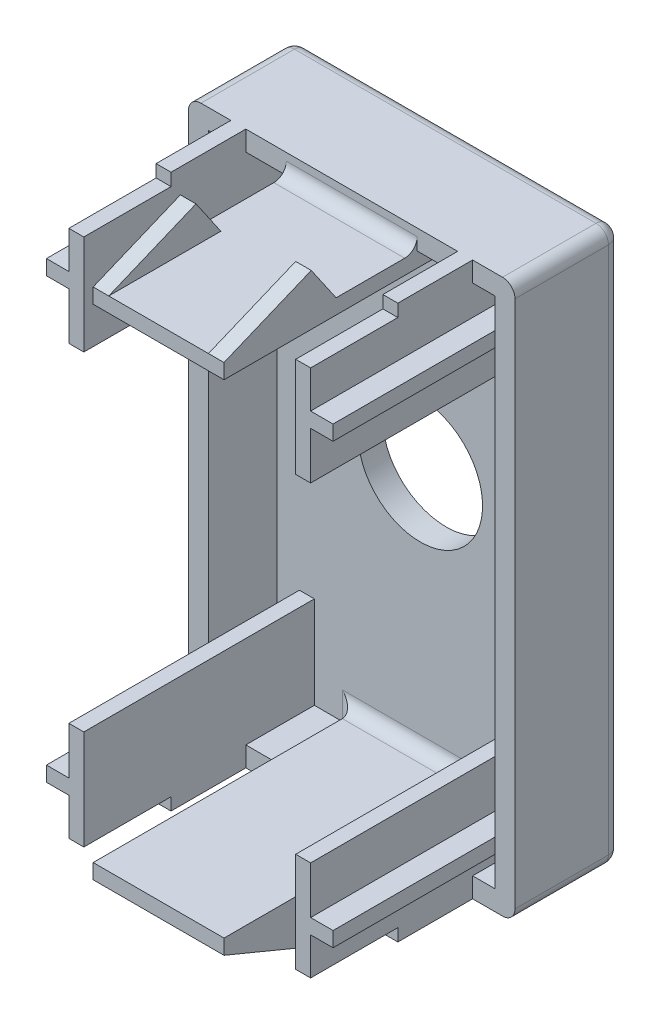
SolidWorks part; units mm, degrees
material "Сталь 3 ГОСТ 535-88"
ref_plane "Спереди" through (0, 0, 0) normal (0, 0, 1) x (1, 0, 0)
ref_plane "Сверху" through (0, 0, 0) normal (0, 1, 0) x (1, 0, 0)
ref_plane "Справа" through (0, 0, 0) normal (1, 0, 0) x (0, 0, -1)
sketch "Эскиз1" plane through (0, 0, 0) normal (0, 0, 1) x (1, 0, 0)
  line L0 (0, 22.2) -> (26.2, 22.2) construction
  line L1 (0, 0) -> (26.2, 0)
  line L2 (0, 0) -> (0, 44.4)
  line L3 (0, 44.4) -> (26.2, 44.4)
  line L4 (26.2, 0) -> (26.2, 44.4)
  circle A0 centre (13.1, 22.2) radius 5
  dimension "D3" = 10
  dimension "D1" = 26.2
  dimension "D2" = 44.4
extrude "Бобышка-Вытянуть1" add sketch "Эскиз1" along normal blind 8.5
ref_plane "Плоскость1" through (3, 0, 0) normal (1, 0, 0) x (0, 0, -1)
sketch "Эскиз2" plane through (3, 0, 0) normal (1, 0, 0) x (0, 0, -1)
  line L0 (0, 0) -> (0, 5) construction
  line L1 (0, 0) -> (0, 44.4) construction
  line L2 (0, 44.4) -> (0, 39.4) construction
  line L3 (0, 39.4) -> (0, 5)
  arc A0 (0, 5) -> (0, 39.4) centre (147.42, 22.2) cw
  dimension "D1" = 5
  dimension "D3" = 1
  dimension "D2" = 5
extrude "Вырез-Вытянуть1" cut sketch "Эскиз2" along normal offset from surface (20.2 mm away) 3 up to face at (26.2, 22.2, 4.25)
sketch "Эскиз3" plane through (0, 0, 8.5) normal (0, 0, 1) x (1, 0, 0)
  line L0 (24.6, 1.6) -> (24.6, 42.8)
  line L1 (26.2, 0) -> (0, 0) construction
  line L2 (26.2, 0) -> (26.2, 44.4) construction
  line L3 (26.2, 44.4) -> (0, 44.4) construction
  line L4 (0, 0) -> (0, 44.4) construction
  line L5 (24.6, 42.8) -> (1.6, 42.8)
  line L6 (1.6, 1.6) -> (1.6, 42.8)
  line L7 (24.6, 1.6) -> (1.6, 1.6)
  dimension "D1" = 1.6
extrude "Вырез-Вытянуть2" cut sketch "Эскиз3" against normal blind 5.5
sketch "Эскиз4" plane through (0, 0, 3) normal (0, 0, 1) x (1, 0, 0)
  line L0 (3.4, 44.4) -> (3.4, 40.4)
  line L1 (24.6, 42.8) -> (1.6, 42.8) construction
  line L2 (3.4, 40.4) -> (1.6, 40.4)
  line L3 (1.6, 42.8) -> (1.6, 1.6) construction
  line L4 (1.6, 40.4) -> (1.6, 39.2)
  line L5 (1.6, 39.2) -> (3.4, 39.2)
  line L6 (3.4, 39.2) -> (3.4, 35.4)
  line L7 (3.4, 35.4) -> (4.6, 35.4)
  line L8 (4.6, 35.4) -> (4.6, 44.4)
  line L10 (4.6, 44.4) -> (3.4, 44.4)
  line L11 (3.4, 39.2) -> (3.4, 40.4) construction
  line L12 (13.1, 42.8) -> (13.1, 1.6) construction
  line L13 (1.6, 1.6) -> (24.6, 1.6) construction
  line L14 (24.6, 22.2) -> (1.6, 22.2) construction
  line L15 (24.6, 1.6) -> (24.6, 42.8) construction
  line L16 (1.6, 42.8) -> (1.6, 1.6) construction
  line L17 (22.8, 39.2) -> (22.8, 40.4) construction
  line L18 (21.6, 44.4) -> (22.8, 44.4)
  line L19 (21.6, 35.4) -> (21.6, 44.4)
  line L20 (22.8, 35.4) -> (21.6, 35.4)
  line L21 (22.8, 39.2) -> (22.8, 35.4)
  line L22 (24.6, 39.2) -> (22.8, 39.2)
  line L23 (24.6, 40.4) -> (24.6, 39.2)
  line L24 (22.8, 40.4) -> (24.6, 40.4)
  line L25 (22.8, 44.4) -> (22.8, 40.4)
  line L26 (22.8, 5.2) -> (22.8, 4) construction
  line L27 (3.4, 5.2) -> (3.4, 4) construction
  line L28 (22.8, 0) -> (22.8, 4)
  line L29 (22.8, 4) -> (24.6, 4)
  line L30 (24.6, 4) -> (24.6, 5.2)
  line L31 (24.6, 5.2) -> (22.8, 5.2)
  line L32 (22.8, 5.2) -> (22.8, 9)
  line L33 (22.8, 9) -> (21.6, 9)
  line L34 (21.6, 9) -> (21.6, 0)
  line L35 (21.6, 0) -> (22.8, 0)
  line L36 (4.6, 0) -> (3.4, 0)
  line L37 (4.6, 9) -> (4.6, 0)
  line L38 (3.4, 9) -> (4.6, 9)
  line L39 (3.4, 5.2) -> (3.4, 9)
  line L40 (1.6, 5.2) -> (3.4, 5.2)
  line L41 (1.6, 4) -> (1.6, 5.2)
  line L42 (3.4, 4) -> (1.6, 4)
  line L43 (3.4, 0) -> (3.4, 4)
  line L44 (26.2, 44.4) -> (0, 44.4) construction
  dimension "D1" = 1.2
  dimension "D2" = 1.2
  dimension "D3" = 4
  dimension "D4" = 9
  dimension "D5" = 1.8
extrude "Бобышка-Вытянуть2" add sketch "Эскиз4" along normal blind 18.5
ref_plane "Плоскость2" through (13.1, 0, 0) normal (-1, 0, 0) x (0, 0, 1)
sketch "Эскиз6" plane through (13.1, 0, 0) normal (-1, 0, 0) x (0, 0, 1)
  line L0 (3, 1.6) -> (3, 2.8)
  line L1 (3, 9) -> (3, 1.6) construction
  line L2 (3, 2.8) -> (24, 2.8)
  line L3 (24, 2.8) -> (24, 1.6)
  line L4 (24, 1.6) -> (17, -1.3)
  line L5 (17, -1.3) -> (15, 1.6)
  line L6 (15, 1.6) -> (3, 1.6)
  line L7 (15, 1.6) -> (24, 1.6) construction
  line L8 (0, 22.2) -> (37.8181, 22.2) construction
  line L9 (0, 39.4) -> (0, 5) construction
  line L10 (15, 42.8) -> (24, 42.8) construction
  line L11 (15, 42.8) -> (3, 42.8)
  line L12 (17, 45.7) -> (15, 42.8)
  line L13 (24, 42.8) -> (17, 45.7)
  line L14 (24, 41.6) -> (24, 42.8)
  line L15 (3, 41.6) -> (24, 41.6)
  line L16 (3, 42.8) -> (3, 41.6)
  dimension "D1" = 1.2
  dimension "D2" = 12
  dimension "D3" = 21
  dimension "D4" = 47
  dimension "D5" = 14
extrude "Бобышка-Вытянуть3" add sketch "Эскиз6" along normal blind 5.25 and the other way blind 5.25
sketch "Эскиз7" plane through (3.4, 0, 0) normal (-1, 0, 0) x (0, 0, 1)
  line L0 (21.5, 4) -> (21.5, 0) construction
  line L1 (21.5, 44.4) -> (14.5, 44.4)
  line L2 (21.5, 44.4) -> (21.5, 43.4)
  line L3 (21.5, 43.4) -> (14.5, 43.4)
  line L4 (14.5, 44.4) -> (14.5, 43.4)
  line L5 (21.5, 0) -> (14.5, 0)
  line L6 (21.5, 0) -> (21.5, 1)
  line L7 (21.5, 1) -> (14.5, 1)
  line L8 (14.5, 0) -> (14.5, 1)
  line L9 (21.5, 0) -> (8.5, 0) construction
  dimension "D1" = 1
  dimension "D2" = 7
  dimension "D3" = 1
  dimension "D4" = 7
extrude "Вырез-Вытянуть3" cut sketch "Эскиз7" against normal blind 3
sketch "Эскиз8" plane through (22.8, 0, 0) normal (1, 0, 0) x (0, 0, -1)
  line L0 (-21.5, 44.4) -> (-8.5, 44.4) construction
  line L1 (-21.5, 0) -> (-14.5, 0)
  line L2 (-21.5, 0) -> (-21.5, 1)
  line L3 (-21.5, 1) -> (-14.5, 1)
  line L4 (-14.5, 0) -> (-14.5, 1)
  line L5 (-21.5, 44.4) -> (-14.5, 44.4)
  line L6 (-21.5, 44.4) -> (-21.5, 43.4)
  line L7 (-21.5, 43.4) -> (-14.5, 43.4)
  line L8 (-14.5, 44.4) -> (-14.5, 43.4)
  dimension "D1" = 1
  dimension "D2" = 1
  dimension "D3" = 7
  dimension "D4" = 7
extrude "Вырез-Вытянуть4" cut sketch "Эскиз8" against normal blind 3
sketch "Эскиз9" plane through (0, 0, 24) normal (0, 0, 1) x (1, 0, 0)
  line L0 (13.1, 1.6) -> (13.1, 0.0848) construction
  line L1 (18.35, 1.6) -> (7.85, 1.6) construction
  line L2 (13.1, 4.675) -> (13.1, -4.675) construction
  line L3 (18.35, 2.8) -> (7.85, 2.8) construction
  line L4 (17.1, 1.6) -> (9.1, 1.6)
  line L5 (17.1, 1.6) -> (17.1, -1.4304)
  line L6 (17.1, -1.4304) -> (9.1, -1.4304)
  line L7 (9.1, 1.6) -> (9.1, -1.4304)
  line L8 (17.1, 1.6) -> (9.1, -1.4304) construction
  line L9 (17.1, -1.4304) -> (9.1, 1.6) construction
  line L10 (0, 22.2) -> (-5.4157, 22.2) construction
  line L11 (0, 44.4) -> (0, 0) construction
  line L12 (17.1, 45.8304) -> (9.1, 42.8) construction
  line L13 (17.1, 42.8) -> (9.1, 45.8304) construction
  line L14 (13.1, 42.8) -> (13.1, 44.3152) construction
  line L15 (9.1, 42.8) -> (9.1, 45.8304)
  line L16 (17.1, 45.8304) -> (9.1, 45.8304)
  line L17 (17.1, 42.8) -> (17.1, 45.8304)
  line L18 (17.1, 42.8) -> (9.1, 42.8)
  dimension "D1" = 8
  dimension "D2" = 1.2
extrude "Вырез-Вытянуть5" cut sketch "Эскиз9" against normal up to surface (15.5 mm away) up to face at (1.9333, 22.2, 8.5)
fillet "Скругление1" radius 1 8 edges at (0, 0, 4.25) (26.2, 0, 4.25) (0, 44.4, 4.25) (26.2, 44.4, 4.25) (13.1, 0, 0) (0, 22.2, 0) (13.1, 44.4, 0) (26.2, 22.2, 0)
fillet "Скругление3" radius 1 8 edges at (7.85, 2.2, 3) (18.35, 2.2, 3) (18.35, 42.2, 3) (7.85, 42.2, 3) (13.1, 41.6, 3) (13.1, 42.8, 8.5) (13.1, 2.8, 3) (13.1, 1.6, 8.5)
